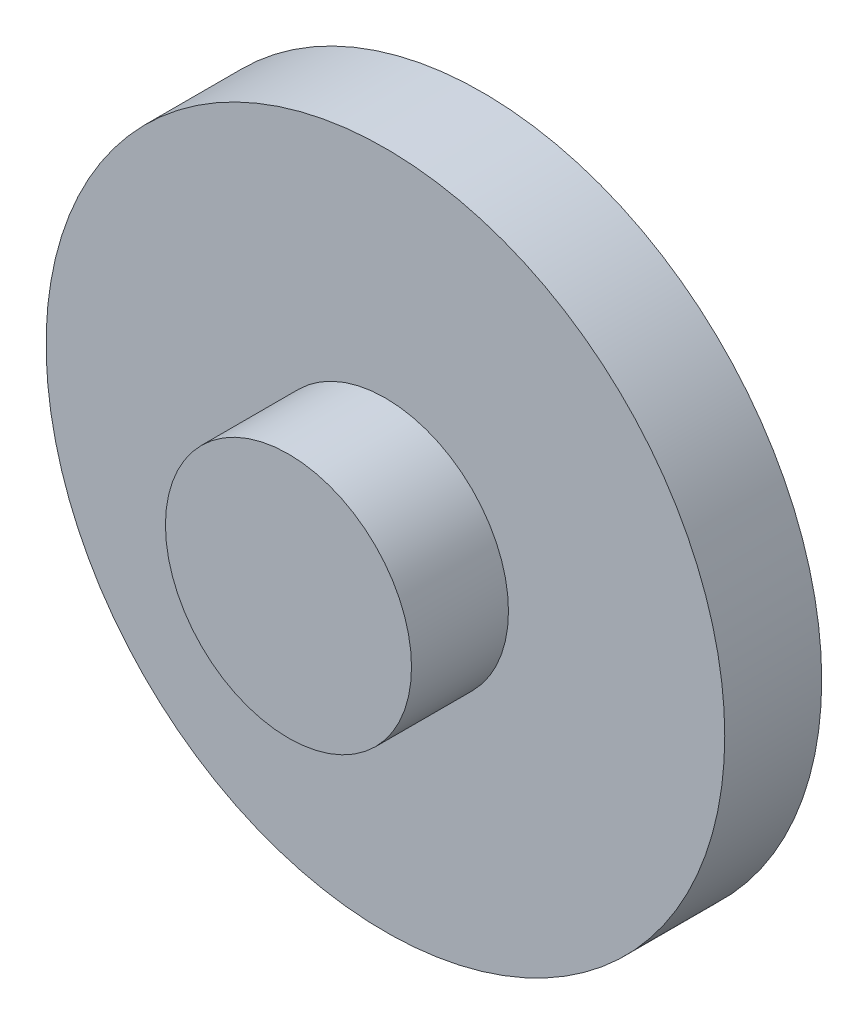
SolidWorks part; units mm, degrees
ref_plane "Front Plane" through (0, 0, 0) normal (0, 0, 1) x (1, 0, 0)
ref_plane "Top Plane" through (0, 0, 0) normal (0, 1, 0) x (1, 0, 0)
ref_plane "Right Plane" through (0, 0, 0) normal (1, 0, 0) x (0, 0, -1)
sketch "Sketch1" plane through (0, 0, 0) normal (0, 0, 1) x (1, 0, 0)
  circle A0 centre (0, 0) radius 17.5
  circle A1 centre (0, 0) radius 6.345
  dimension "D1" = 35
  dimension "D2" = 12.69
extrude "Boss-Extrude1" add sketch "Sketch1" along normal blind 5
extrude "Boss-Extrude2" add sketch "Sketch1<2>" along normal blind 10 contours A1
sketch "Sketch1<2>" plane through (0, 0, 0) normal (0, 0, 1) x (1, 0, 0) same geometry as "Sketch1"
